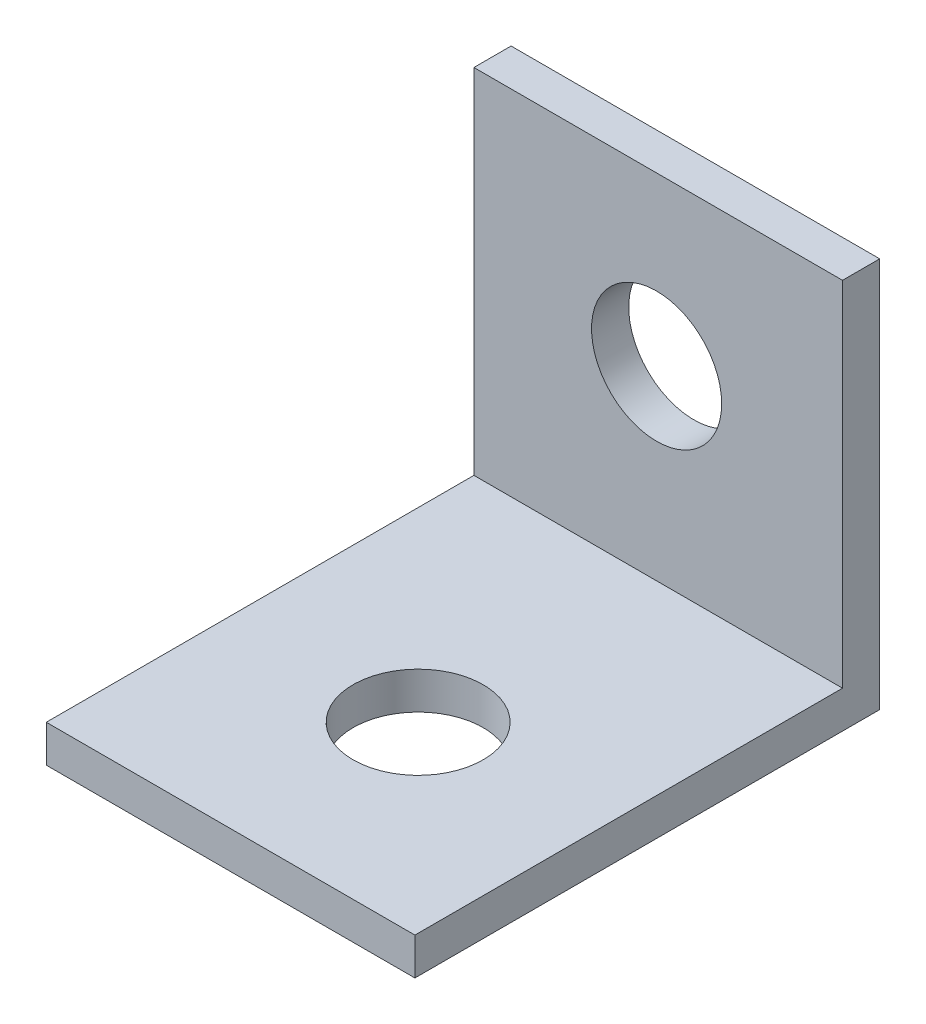
SolidWorks part; units mm, degrees
ref_plane "Front Plane" through (0, 0, 0) normal (0, 0, 1) x (1, 0, 0)
ref_plane "Top Plane" through (0, 0, 0) normal (0, 1, 0) x (1, 0, 0)
ref_plane "Right Plane" through (0, 0, 0) normal (1, 0, 0) x (0, 0, -1)
sketch "Sketch1" plane through (0, 0, 0) normal (0, 1, 0) x (1, 0, 0)
  line L1 (0, 0) -> (9.9133, 0)
  line L2 (0, 0) -> (0, 12.5)
  line L3 (0, 12.5) -> (9.9133, 12.5)
  line L4 (9.9133, 0) -> (9.9133, 12.5)
  line L5 (0, 12.5) -> (9.9133, 12.5)
  line L6 (0, 12.5) -> (0, 11.5)
  line L7 (0, 11.5) -> (9.9133, 11.5)
  line L8 (9.9133, 12.5) -> (9.9133, 11.5)
  circle A0 centre (5, 5) radius 1.75
  dimension "D1" = 5
  dimension "D3" = 7.5
  dimension "D5" = 3.5
  dimension "D2" = 5
  dimension "D4" = 1
extrude "Boss-Extrude3" add sketch "Sketch1" along normal blind 1 contours L7 L2 L1 L4 A0 region at (0.1518, 0, -5.75)
extrude "Boss-Extrude4" add sketch "Sketch1<5>" along normal blind 10.5 contours L2 L7 L4 L3 region at (4.9566, 0, -12)
sketch "Sketch1<5>" plane through (0, 0, 0) normal (0, 1, 0) x (1, 0, 0) same geometry as "Sketch1"
sketch "Sketch2" plane through (0, 0, -11.5) normal (0, 0, 1) x (1, 0, 0)
  line L0 (9.9133, 10.5) -> (9.9133, 1) construction
  line L1 (0, 0) -> (9.9133, 0) construction
  circle A0 centre (4.9133, 6) radius 1.75
  dimension "D1" = 5
  dimension "D2" = 6
  dimension "D3" = 3.5
extrude "Cut-Extrude1" cut sketch "Sketch2" against normal blind 1
